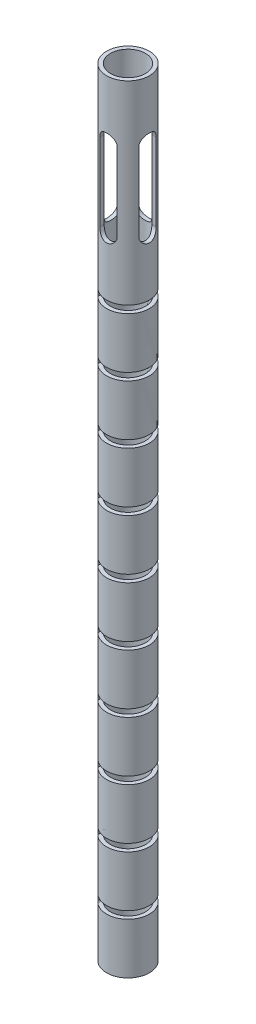
SolidWorks part; units mm, degrees
material "Duranickel(R) 301"
ref_plane "Front Plane" through (0, 0, 0) normal (0, 0, 1) x (1, 0, 0)
ref_plane "Top Plane" through (0, 0, 0) normal (0, 1, 0) x (1, 0, 0)
ref_plane "Right Plane" through (0, 0, 0) normal (1, 0, 0) x (0, 0, -1)
sketch "Sketch2" plane through (0, 0, 0) normal (0, 1, 0) x (1, 0, 0)
  circle A0 centre (0, 0) radius 0.45
  circle A1 centre (0, 0) radius 0.55
  dimension "D1" = 1.1
  dimension "D2" = 0.9
extrude "Boss-Extrude1" add sketch "Sketch2" along normal blind 20
sketch "Sketch3" plane through (0, 0, 0) normal (0, 1, 0) x (1, 0, 0)
  line L0 (-0.385, -0.4602) -> (-0.385, 0.4602)
  arc A0 (-0.385, -0.4602) -> (-0.385, 0.4602) centre (0, 0) ccw
  dimension "D2" = 0.6
  dimension "D1" = 0.385
extrude "Cut-Extrude1" cut sketch "Sketch3" against normal blind 0.1901 from offset 1.5
ref_axis "Axis1" through (0, 31.5, 0) along (0, -1, 0)
pattern_linear "LPattern2" count 10 spacing 1.5 along (0, 1, 0) of "Cut-Extrude1"
sketch "Sketch5" plane through (0, 0, 0) normal (0, 0, 1) x (1, 0, 0)
  line L0 (0, 18.5) -> (0, 16.5) construction
  line L1 (0.225, 18.5) -> (0.225, 16.5)
  line L2 (-0.225, 18.5) -> (-0.225, 16.5)
  line L3 (0.45, 20) -> (-0.45, 20) construction
  arc A0 (0.225, 18.5) -> (-0.225, 18.5) centre (0, 18.5) ccw
  arc A1 (-0.225, 16.5) -> (0.225, 16.5) centre (0, 16.5) ccw
  point P2 (0, 17.5)
  dimension "D2" = 0.45
  dimension "D1" = 2
  dimension "D3" = 2.5
extrude "Cut-Extrude3" cut sketch "Sketch5" against normal through all
pattern_circular "CirPattern2" count 4 over 360 about axis through (0, 31.5, 0) along (0, -1, 0) of "Cut-Extrude3"
fillet "Fillet2" radius 0.02 2 edges at (-0.385, 1.5, 0.3129) (-0.385, 1.3099, 0.3129)
ref_plane "Plane1" through (0.55, 0, 0) normal (1, 0, 0) x (0, 0, -1)
sketch "Sketch6" plane through (0.55, 0, 0) normal (1, 0, 0) x (0, 0, -1)
  line L0 (0, 0) -> (0, 20) construction
  line L1 (0.55, 20) -> (-0.55, 20) construction
equation "\"l\"= 15mm"
equation "\"u\"= 1.3099"
equation "\"h\"= 0.1901mm"
equation "\"D1@Boss-Extrude1\"=\"l\"+5mm"
equation "\"D19@Cut-Extrude1\"=\"u\"+\"h\""
equation "\"D1@Cut-Extrude1\"=\"h\""
equation "\"D3@LPattern2\"=\"u\"+\"h\""
